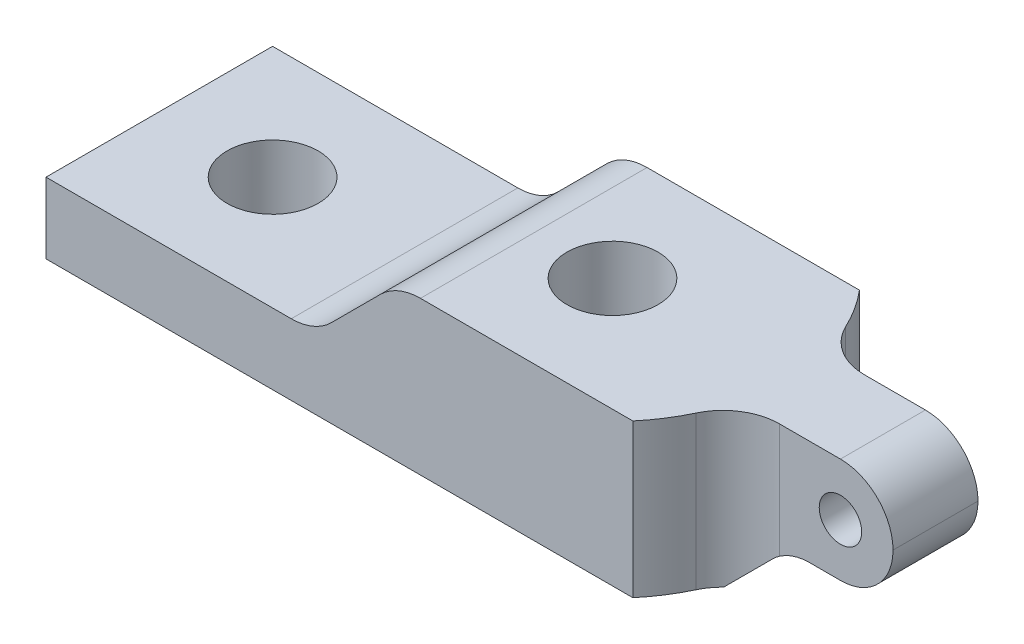
SolidWorks part; units mm, degrees
material "6061 Alloy"
ref_plane "Front" through (0, 0, 0) normal (0, 0, 1) x (1, 0, 0)
ref_plane "Top" through (0, 0, 0) normal (0, 1, 0) x (1, 0, 0)
ref_plane "Right" through (0, 0, 0) normal (1, 0, 0) x (0, 0, -1)
sketch "Sketch1" plane through (0, 0, 0) normal (0, 0, 1) x (1, 0, 0)
  line L0 (0, 0) -> (6.35, 0) construction
  line L1 (2.9464, -11.9837) -> (-40.5587, -11.9837) construction
  line L2 (-40.5587, 2.9464) -> (2.9464, 2.9464)
  line L3 (2.9464, 2.9464) -> (2.9464, -2.9464)
  line L4 (2.9464, -2.9464) -> (-2.9464, -2.9464)
  line L5 (-2.9464, -2.9464) -> (-5.6337, -5.6337)
  line L6 (-5.6337, -5.6337) -> (-40.5587, -5.6337)
  line L7 (-40.5587, -5.6337) -> (-40.5587, 2.9464)
  line L8 (-5.6337, -5.6337) -> (2.9464, -5.6337) construction
  line L9 (2.9464, -5.6337) -> (2.9464, -2.9464) construction
  circle A0 centre (0, 0) radius 2.9464 construction
  circle A1 centre (6.35, 0) radius 2.9464 construction
  circle A2 centre (0, 0) radius 1.1906
  dimension "D1" = 5.8928
  dimension "D4" = 2.3813
  dimension "D2" = 6.35
  dimension "D3" = 11.9837
  dimension "D5" = 6.35
  dimension "D6" = 5.8928
  dimension "D7" = 34.925
  dimension "D8" = 45
extrude "Boss-Extrude1" add sketch "Sketch1" along normal blind 12.7
sketch "Sketch2" plane through (0, -5.6337, 0) normal (0, -1, 0) x (1, 0, 0)
  line L0 (-5.6337, 12.7) -> (-5.6337, 0) construction
  line L1 (2.9464, 12.7) -> (-5.6337, 12.7)
  line L2 (2.9464, 12.7) -> (2.9464, 8.7312)
  line L3 (2.9464, 8.7312) -> (-5.6337, 8.7312)
  line L4 (-5.6337, 12.7) -> (-5.6337, 8.7312)
  line L5 (-1.3437, 8.7312) -> (-1.3437, 3.9688) construction
  line L6 (2.9464, 0) -> (-5.6337, 0)
  line L7 (2.9464, 0) -> (2.9464, 3.9688)
  line L8 (2.9464, 3.9688) -> (-5.6337, 3.9688)
  line L9 (-5.6337, 0) -> (-5.6337, 3.9688)
  line L10 (-1.3437, 6.35) -> (2.9464, 6.35) construction
  line L11 (2.9464, 12.7) -> (2.9464, 0) construction
  dimension "D1" = 4.7625
extrude "Cut-Extrude1" cut sketch "Sketch2" against normal through all
fillet "Fillet1" radius 2.9464 3 edges at (-2.9464, -2.9464, 6.35) (2.9464, -2.9464, 6.35) (2.9464, 2.9464, 6.35)
sketch "Sketch3" plane through (0, -5.6337, 0) normal (0, -1, 0) x (1, 0, 0)
  line L0 (-40.5587, 6.35) -> (-5.6337, 6.35) construction
  line L1 (-40.5587, 12.7) -> (-40.5587, 0) construction
  line L2 (-5.6337, 8.7312) -> (-5.6337, 3.9688) construction
  line L3 (-34.804, 6.35) -> (-26.8665, 6.35) construction
  line L4 (-34.804, 8.9297) -> (-26.8665, 8.9297)
  line L5 (-34.804, 3.7703) -> (-26.8665, 3.7703)
  line L6 (-15.754, 6.35) -> (-7.8165, 6.35) construction
  line L7 (-15.754, 8.9297) -> (-7.8165, 8.9297)
  line L8 (-15.754, 3.7703) -> (-7.8165, 3.7703)
  line L9 (-37.3837, 12.7) -> (-37.3837, 0) construction
  line L10 (-40.5587, 12.7) -> (-5.6337, 12.7) construction
  line L11 (-40.5587, 0) -> (-5.6337, 0) construction
  arc A0 (-34.804, 8.9297) -> (-34.804, 3.7703) centre (-34.804, 6.35) ccw
  arc A1 (-26.8665, 3.7703) -> (-26.8665, 8.9297) centre (-26.8665, 6.35) ccw
  arc A2 (-15.754, 8.9297) -> (-15.754, 3.7703) centre (-15.754, 6.35) ccw
  arc A3 (-7.8165, 3.7703) -> (-7.8165, 8.9297) centre (-7.8165, 6.35) ccw
  point P8 (-30.8353, 6.35)
  point P13 (-11.7853, 6.35)
  dimension "D1" = 5.1594
  dimension "D2" = 7.9375
  dimension "D3" = 3.175
  dimension "D4" = 19.05
extrude "Cut-Extrude2" [suppressed] cut sketch "Sketch3" against normal through all
hole_wizard "#10 Clearance Hole1" positions "Sketch4" profile "Sketch5" hole size "#10" standard "ANSI Inch" end condition through all
sketch "Sketch4" plane through (0, -5.6337, 0) normal (0, -1, 0) x (-1, 0, 0)
  line L0 (5.6337, -6.35) -> (40.5587, -6.35) construction
  line L1 (5.6337, -8.7312) -> (5.6337, -3.9688) construction
  line L2 (40.5587, -12.7) -> (40.5587, 0) construction
  point P9 (15.1587, -6.35)
  point P11 (34.2087, -6.35)
  dimension "D1" = 9.525
  dimension "D2" = 19.05
sketch "Sketch5" plane through (-34.2087, -5.6337, 6.35) normal (1, 0, 0) x (0, 0, -1)
  line L0 (0, 0) -> (0, 8.5801)
  line L1 (0, 8.5801) -> (2.5527, 8.5801)
  line L2 (2.5527, 8.5801) -> (2.5527, 0)
  line L5 (2.5527, 0) -> (0, 0)
  line L11 (0, -6.35) -> (0, 107.95) construction
  dimension "Thru Hole Dia." = 5.1054
  dimension "Thru Hole Depth" = 8.5801
sketch "Sketch6" plane through (0, 0, 12.7) normal (0, 0, 1) x (1, 0, 0)
  line L0 (-40.5587, 2.9464) -> (-20.8864, 2.9464)
  line L1 (-5.6337, 2.9464) -> (-40.5587, 2.9464) construction
  line L2 (-20.8864, 2.9464) -> (-25.4978, -1.665)
  line L3 (-25.4978, -1.665) -> (-40.5587, -1.665)
  line L4 (-40.5587, 2.9464) -> (-40.5587, -5.6337) construction
  line L5 (-40.5587, -1.665) -> (-40.5587, 2.9464)
  line L6 (-40.5587, -5.6337) -> (-5.6337, -5.6337) construction
  dimension "D1" = 3.175
  dimension "D2" = 45
  dimension "D3" = 3.9688
extrude "Cut-Extrude3" cut sketch "Sketch6" against normal through all
fillet "Fillet2" radius 3.175 2 edges at (-25.4978, -1.665, 6.35) (-20.8864, 2.9464, 6.35)
sketch "Sketch7" plane through (0, 2.9464, 0) normal (0, 1, 0) x (1, 0, 0)
  line L0 (-5.6337, -12.7) -> (-19.5713, -12.7) construction
  line L1 (-5.6337, 0) -> (-19.5713, 0) construction
  line L2 (-7.6705, 0) -> (-5.6337, 0)
  line L3 (-5.6337, 0) -> (-5.6337, -3.9688)
  line L4 (-5.6337, -8.7312) -> (-5.6337, -12.7)
  line L5 (-5.6337, -12.7) -> (-7.6705, -12.7)
  arc A0 (-5.6337, -8.7312) -> (-7.6705, -12.7) centre (-15.1587, -6.35) cw
  arc A1 (-5.6337, -3.9688) -> (-7.6705, 0) centre (-15.1587, -6.35) ccw
extrude "Cut-Extrude4" cut sketch "Sketch7" against normal through all
fillet "Fillet3" radius 3.175 2 edges at (-5.6337, -1.3437, 3.9688) (-5.6337, -1.3437, 8.7312)
